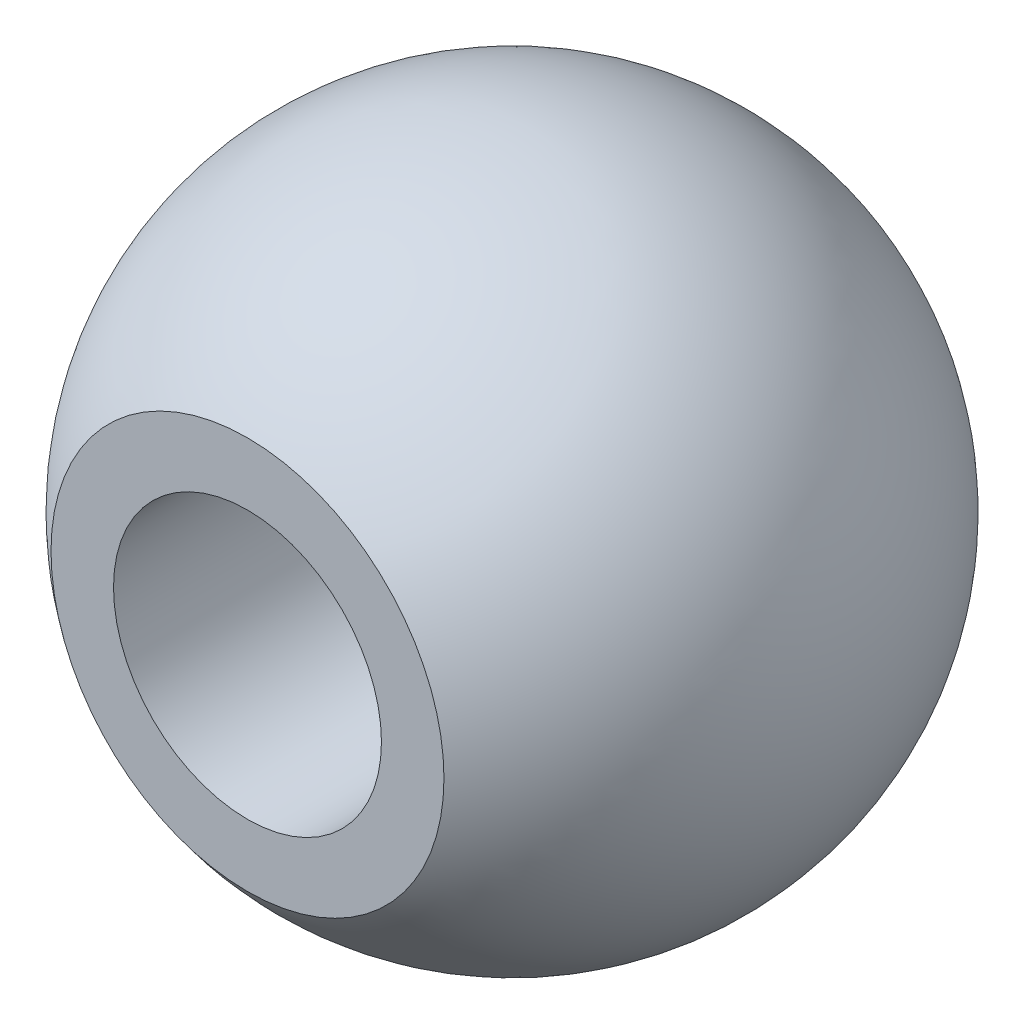
SolidWorks part; units mm, degrees
ref_plane "Front Plane" through (0, 0, 0) normal (0, 0, 1) x (1, 0, 0)
ref_plane "Top Plane" through (0, 0, 0) normal (0, 1, 0) x (1, 0, 0)
ref_plane "Right Plane" through (0, 0, 0) normal (1, 0, 0) x (0, 0, -1)
sketch "Sketch1" plane through (0, 0, 0) normal (0, 0, 1) x (1, 0, 0)
  line L0 (0, 2.46) -> (0, -2.46) construction
  line L1 (0, 2.46) -> (0, -2.46)
  arc A0 (0, 2.46) -> (0, -2.46) centre (0, 0) ccw
  dimension "D1" = 4.92
revolve "Revolve1" add sketch "Sketch1" angle 360 about L0
sketch "Sketch2" plane through (0, 0, 0) normal (0, 0, 1) x (1, 0, 0)
  circle A0 centre (0, 0) radius 1
  dimension "D1" = 2
extrude "Cut-Extrude1" cut sketch "Sketch2" against normal blind 10 and the other way blind 10
sketch "Sketch3" plane through (0, 0, 0) normal (0, 1, 0) x (1, 0, 0)
  line L1 (3.2962, -1.975) -> (-3.2962, -1.975)
  line L2 (3.2962, -1.975) -> (3.2962, 1.975)
  line L3 (3.2962, 1.975) -> (-3.2962, 1.975)
  line L4 (-3.2962, -1.975) -> (-3.2962, 1.975)
  line L5 (3.2962, -1.975) -> (-3.2962, 1.975) construction
  line L6 (3.2962, 1.975) -> (-3.2962, -1.975) construction
  point P0 (0, 0)
  dimension "D1" = 3.95
extrude "Cut-Extrude2" cut sketch "Sketch3" against normal blind 10 and the other way blind 10 flip side to cut
